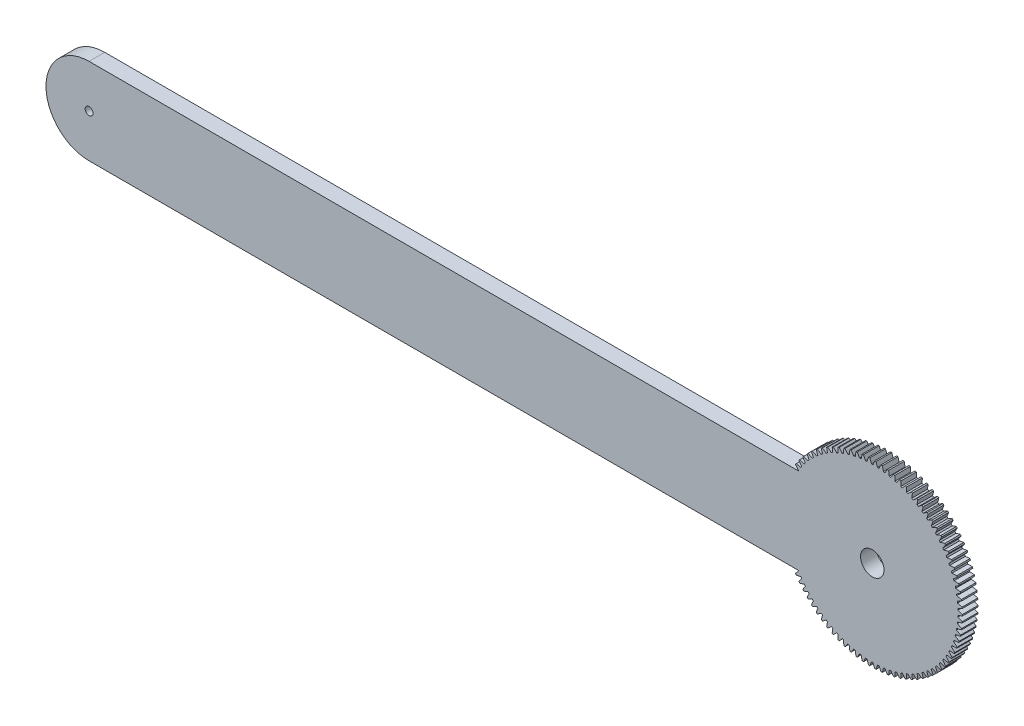
SolidWorks part; units mm, degrees
material "Alumina"
ref_plane "Plane1" through (0, 0, 0) normal (0, 0, 1) x (1, 0, 0)
ref_plane "Plane2" through (0, 0, 0) normal (0, 1, 0) x (1, 0, 0)
ref_plane "Plane3" through (0, 0, 0) normal (1, 0, 0) x (0, 0, -1)
sketch "HoldingSke" plane through (0, 0, 0) normal (0, 1, 0) x (1, 0, 0)
  line L0 (0, 0) -> (0, -2)
  line L1 (-15, 0) -> (100, 0) construction
  line L2 (0, 0) -> (-2.1039, 2.3779)
  line L3 (0, 0) -> (-11.863, 4.5341)
  line L4 (0, 0) -> (0, 8.636)
  line L5 (0, 0) -> (-46.8476, -17.4728)
  line L6 (0, 0) -> (-3.3159, -2.2372)
  line L7 (-2.1039, 2.3779) -> (8.6586, 51.2059)
  line L8 (-76.2, 54.61) -> (-74.4, 54.61)
  line L9 (-71.009, 38.7566) -> (-53.1078, 45.2721)
  line L10 (-76.2, 71.12) -> (104.1128, 71.12)
  line L11 (0, 0) -> (-4, 0)
  line L12 (-76.2, 101.6) -> (-76.181, 101.6)
  line L13 (24.9733, 27.94) -> (52.9518, 28.4284)
  line L14 (24.9733, 27.94) -> (24.9743, 27.94)
  line L15 (24.9733, 27.94) -> (100.4006, 29.5858)
  line L16 (-63.627, -0.5) -> (-12.827, -0.5)
  circle A0 centre (0, 0) radius 5
  circle A1 centre (0, 0) radius 21.874
  circle A2 centre (0, 0) radius 37.5
  circle A3 centre (0, 0) radius 5
  dimension "MHD" = 43.748
  dimension "Hub_dia" = 75
  dimension "Bore" = 10
  dimension "MBD" = 10
  dimension "Num_teeth" = 90
  dimension "Pitch" = 2
  dimension "Overall_len" = 50
  dimension "Show_teeth" = 90
  dimension "Thickness" = 4
  dimension "OAL" = 50.0001
  dimension "T_dim" = 1.8
  dimension "Ap" = 20
  dimension "H" = 19.05
  dimension "Pitch_radius" = 180.3128
  dimension "Width" = 4
  dimension "Backlash" = 0.019
  dimension "Addendum_fac" = 1
  dimension "Dedendum_fac" = 1.25
  dimension "Clearance_fac" = 0.25
  dimension "Dedendum_add" = 0.001
  dimension "Module" = 0.5
sketch "BasProSke" plane through (0, 0, 0) normal (0, 1, 0) x (1, 0, 0)
  line L0 (-10, 0) -> (60, 0) construction
  line L1 (0, 0) -> (0, 23)
  line L2 (0, 0) -> (4, 0)
  line L3 (4, 0) -> (4, 23)
  line L4 (4, 23) -> (0, 23)
  dimension "Thickness" = 4
  dimension "Diameter" = 46
revolve "Base-Revolve" add sketch "BasProSke" angle 360 about L0
sketch "TooCutSke" plane through (0, 0, 0) normal (1, 0, 0) x (0, 0, -1)
  line L1 (0, 0) -> (0, 107) construction
  line L2 (0, 0) -> (-0.4259, 22.496) construction
  line L3 (0, 0) -> (-1.5703, 44.9668) construction
  line L4 (-0.4259, 22.496) -> (-0.7851, 22.4834) construction
  arc A0 (0.2085, 21.873) -> (-0.2085, 21.873) centre (0, 0) ccw
  arc A1 (0.6483, 23.0163) -> (-0.6483, 23.0163) centre (0, 0) ccw
  circle A2 centre (0, 0) radius 22.5 construction
  circle A3 centre (0, 0) radius 21.1431 construction
  arc A4 (-0.2085, 21.873) -> (-0.6483, 23.0163) centre (-8.8088, 19.2207) ccw
  arc A5 (0.6483, 23.0163) -> (0.2085, 21.873) centre (8.8088, 19.2207) ccw
  dimension "Root_dia" = 43.748
  dimension "Overcut_dia" = 46.0508
  dimension "Pitch_dia" = 45
  dimension "Base_dia" = 42.2862
  dimension "Flank_rad" = 9
  dimension "Half_ang" = 2
  dimension "Half_CT" = 0.3594
extrude "ToothCut" cut sketch "TooCutSke" along normal through all
fillet "Breaks" [suppressed] radius 0.01 tangent propagation no
fillet "RootFillets" [suppressed] radius 0.126
pattern_circular "TeethCuts" count 90 every 4 about axis through (-10, 0, 0) along (1, 0, 0) of "ToothCut", "RootFillets", "Breaks"
sketch "HubNeaOneSke" plane through (0, 0, 0) normal (-1, 0, 0) x (0, 0, 1)
  circle A0 centre (0, 0) radius 21.874
  dimension "Diameter" = 43.748
extrude "HubNearOne" [suppressed] add sketch "HubNeaOneSke" along normal blind 46.0001
sketch "HubNeaBotSke" plane through (0, 0, 0) normal (-1, 0, 0) x (0, 0, 1)
  circle A0 centre (0, 0) radius 21.874
  dimension "Diameter" = 43.748
extrude "HubNearBoth" [suppressed] add sketch "HubNeaBotSke" along normal blind 23
ref_plane "FarPln" through (4, 0, 0) normal (1, 0, 0) x (0, 0, -1)
sketch "HubFarSke" plane through (4, 0, 0) normal (1, 0, 0) x (0, 0, -1)
  circle A0 centre (0, 0) radius 21.874
  dimension "Diameter" = 43.748
extrude "HubFar" [suppressed] add sketch "HubFarSke" along normal blind 23
sketch "BorSke" plane through (0, 0, 0) normal (1, 0, 0) x (0, 0, -1)
  circle A0 centre (0, 0) radius 5
  dimension "Diameter" = 10
extrude "Bore" cut sketch "BorSke" along normal mid plane 100.0001
sketch "KeySke" plane through (0, 0, 0) normal (1, 0, 0) x (0, 0, -1)
  line L0 (-2, 0) -> (-2, 6.8)
  line L1 (-2, 6.8) -> (2, 6.8)
  line L2 (2, 6.8) -> (2, 0)
  line L3 (0, 0) -> (0, 34) construction
  line L4 (-2, 0) -> (2, 0)
  dimension "Width" = 4
  dimension "Offset" = 6.8
extrude "Keyway" [suppressed] cut sketch "KeySke" along normal mid plane 100.0001
pattern_circular "Keyway2" [suppressed] count 2 every 90 about axis through (-10, 0, 0) along (1, 0, 0) reverse direction yes
sketch "Sketch1" plane through (0, 0, 0) normal (1, 0, 0) x (0, 0, -1)
  line L0 (0, 0) -> (-200, 0) construction
  line L1 (0, -11) -> (-200, -11)
  line L2 (0, 11) -> (-200, 11)
  arc A0 (0, -11) -> (0, 11) centre (0, 0) ccw
  arc A1 (-200, 11) -> (-200, -11) centre (-200, 0) ccw
  point P3 (-100, 0)
extrude "Boss-Extrude1" add sketch "Sketch1" along normal blind 4 contours L2 A1 L1 A0
sketch "Sketch3" plane through (0, 0, 0) normal (1, 0, 0) x (0, 0, -1)
  circle A2 centre (-200, 0) radius 1
extrude "Cut-Extrude2" cut sketch "Sketch3" along normal through all contours A2 region at (0, 0, 200)
sketch "Sketch4" plane through (0, 0, 0) normal (1, 0, 0) x (0, 0, -1)
  circle A0 centre (0, 0) radius 3
extrude "Cut-Extrude4" cut sketch "Sketch4" along normal through all
move or copy body "Body-Move/Copy1" bodies to move or copy 106 copy no rotation origin (2, 0, 94) rotation axis (0, 1, 0) rotation angle 90
move or copy body "Body-Move/Copy2" bodies to move or copy 107 copy no rotation origin (2, 0, 0) rotation axis (0, 0, 1) rotation angle 180
equation "' \"Module@HoldingSke\" = 6.35"
equation "' \"Num_teeth@HoldingSke\" = 12"
equation "' \"Ap@HoldingSke\" =  20"
equation "' \"Ap@HoldingSke\" = 20"
equation "' \"Width@HoldingSke\" = 0.5 * 25.4"
equation "' \"Hub_dia@HoldingSke\"= 1 * 25.4"
equation "' \"Hub_dia@HoldingSke\" = 1 * 25.4"
equation "' \"Overall_len@HoldingSke\" = 1.0 * 25.4"
equation "' \"Bore@HoldingSke\" = 0.75 * 25.4"
equation "' \"T_dim@HoldingSke\" = 0.1 * 25.4"
equation "' \"Width@KeySke\" = 0.25 * 25.4"
equation "' \"Show_teeth@HoldingSke\" = 13"
equation "' \"Backlash@HoldingSke\" = 0.009 * 25.4"
equation "' \"Addendum_fac@HoldingSke\" = 1.0"
equation "' \"Dedendum_fac@HoldingSke\" = 1.25"
equation "' \"Dedendum_add@HoldingSke\" = 0.00005 * 25.4"
equation "' \"Clearance_fac@HoldingSke\" = 0.25"
equation "\"Pitch@HoldingSke\" = 1 / \"Module@HoldingSke\""
equation "\"Overcut_dia@TooCutSke\" = (\"Num_teeth@HoldingSke\" + 2 * \"Addendum_fac@HoldingSke\") / \"Pitch@HoldingSke\" + 0.002 * 25.4"
equation "\"Pitch_dia@TooCutSke\" = \"Num_teeth@HoldingSke\" / \"Pitch@HoldingSke\""
equation "\"Base_dia@TooCutSke\" = \"Num_teeth@HoldingSke\" / \"Pitch@HoldingSke\" * cos((\"Ap@HoldingSke\"  * 3.14159265 / 180))"
equation "\"Root_dia@TooCutSke\" = (\"Num_teeth@HoldingSke\" + 2) / \"Pitch@HoldingSke\" - 2 * (\"Addendum_fac@HoldingSke\" + \"Dedendum_fac@HoldingSke\") / \"Pitch@HoldingSke\" - \"Dedendum_add@HoldingSke\" * 2"
equation "\"Half_ang@TooCutSke\" = 180 / \"Num_teeth@HoldingSke\""
equation "\"Half_CT@TooCutSke\" = \"Num_teeth@HoldingSke\" / \"Pitch@HoldingSke\" * sin((3.14159265 / 2 / \"Num_teeth@HoldingSke\")) / 2 - 7 * \"Backlash@HoldingSke\" / 4"
equation "\"Flank_rad@TooCutSke\" = \"Num_teeth@HoldingSke\" / \"Pitch@HoldingSke\" / 5"
equation "\"Radius@RootFillets\" = \"Clearance_fac@HoldingSke\" / \"Pitch@HoldingSke\" + \"Dedendum_add@HoldingSke\""
equation "\"Break_rad@Breaks\" = 0.02 / \"Pitch@HoldingSke\""
equation "\"Thickness@HoldingSke\" = \"Width@HoldingSke\""
equation "\"OAL@HoldingSke\" = \"Thickness@HoldingSke\""
equation "\"MHD@HoldingSke\" = (\"Num_teeth@HoldingSke\" + 2) / \"Pitch@HoldingSke\" - 2 * (\"Addendum_fac@HoldingSke\" + \"Dedendum_fac@HoldingSke\")  / \"Pitch@HoldingSke\" - \"Dedendum_add@HoldingSke\" * 2"
equation "\"MBD@HoldingSke\" = (\"Num_teeth@HoldingSke\" + 2) / \"Pitch@HoldingSke\" - 2 * (\"Addendum_fac@HoldingSke\" + \"Dedendum_fac@HoldingSke\")  / \"Pitch@HoldingSke\" - \"Dedendum_add@HoldingSke\" * 2 - 0.002 * 25.4"
equation "\"MHD@HoldingSke\" = ((sgn( \"MHD@HoldingSke\" - \"Hub_dia@HoldingSke\" )-1)*( \"MHD@HoldingSke\" - \"Hub_dia@HoldingSke\" ))/-2+ \"Hub_dia@HoldingSke\""
equation "\"MBD@HoldingSke\" = ((sgn( \"MBD@HoldingSke\" - \"Bore@HoldingSke\" )-1)*( \"MBD@HoldingSke\" - \"Bore@HoldingSke\" ))/-2+ \"Bore@HoldingSke\""
equation "\"OAL@HoldingSke\" = ((sgn( \"OAL@HoldingSke\" - \"Overall_len@HoldingSke\" )+1)*( \"OAL@HoldingSke\" - \"Overall_len@HoldingSke\" ))/2 + \"Overall_len@HoldingSke\" + 0.000002 * 25.4"
equation "\"Num_teeth@TeethCuts\" = int( \"Show_teeth@HoldingSke\" ) + 1"
equation "\"Num_teeth@TeethCuts\" = ((sgn( \"Num_teeth@TeethCuts\" - \"Num_teeth@HoldingSke\" )-1)*( \"Num_teeth@TeethCuts\" - \"Num_teeth@HoldingSke\" ))/-2+ \"Num_teeth@HoldingSke\""
equation "\"Num_teeth@TeethCuts\" = ((sgn( \"Num_teeth@TeethCuts\" - 2.0)+1)*( \"Num_teeth@TeethCuts\" - 2.0))/2 +2.0"
equation "\"Angle@TeethCuts\" = 360.0 / \"Num_teeth@HoldingSke\""
equation "\"Diameter@BasProSke\" = (\"Num_teeth@HoldingSke\" + 2 * \"Addendum_fac@HoldingSke\") / \"Pitch@HoldingSke\""
equation "\"Thickness@BasProSke\"  = \"Thickness@HoldingSke\""
equation "' \"Fillet_rad@BasProSke\" =  \"Thickness@HoldingSke\" * 0.05"
equation "' \"Fillet_rad@BasProSke\" = \"Thickness@HoldingSke\" * 0.05"
equation "\"MHD@HoldingSke\" = ((sgn( \"MHD@HoldingSke\" - \"Root_dia@TooCutSke\" )-1)*( \"MHD@HoldingSke\" - \"Root_dia@TooCutSke\" ))/-2+ \"Root_dia@TooCutSke\""
equation "\"Diameter@HubNeaOneSke\" = \"MHD@HoldingSke\""
equation "\"Length@HubNearOne\" = \"OAL@HoldingSke\" - \"Thickness@BasProSke\""
equation "\"Diameter@HubNeaBotSke\" = \"MHD@HoldingSke\""
equation "\"Length@HubNearBoth\" = ( \"OAL@HoldingSke\" - \"Thickness@BasProSke\" ) / 2.0"
equation "\"Thickness@FarPln\" = \"Thickness@BasProSke\""
equation "\"Diameter@HubFarSke\" = \"MHD@HoldingSke\""
equation "\"Length@HubFar\" = ( \"OAL@HoldingSke\" - \"Thickness@BasProSke\" ) / 2.0"
equation "\"Diameter@BorSke\" = \"MBD@HoldingSke\""
equation "\"D1@Bore\" = \"OAL@HoldingSke\" * 2.0"
equation "\"D1@Keyway\" = \"OAL@HoldingSke\" * 2.0"
equation "\"Offset@KeySke\" = \"T_dim@HoldingSke\" + \"MBD@HoldingSke\" / 2.0"
